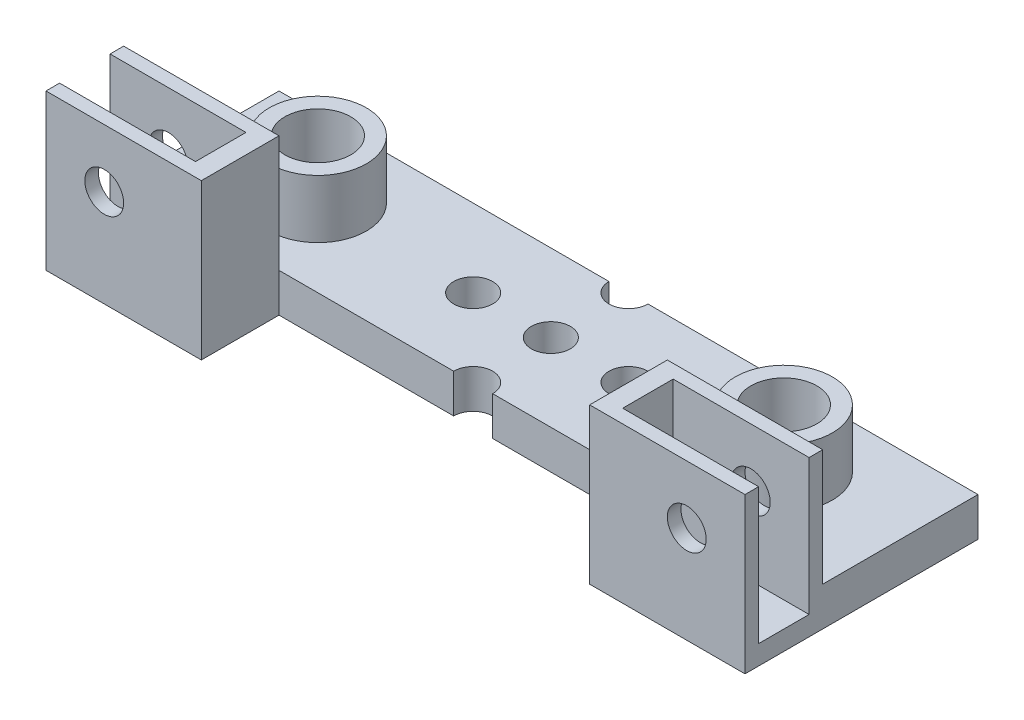
SolidWorks part; units mm, degrees
ref_plane "Front Plane" through (0, 0, 0) normal (0, 0, 1) x (1, 0, 0)
ref_plane "Top Plane" through (0, 0, 0) normal (0, 1, 0) x (1, 0, 0)
ref_plane "Right Plane" through (0, 0, 0) normal (1, 0, 0) x (0, 0, -1)
sketch "Sketch1" plane through (0, 0, 0) normal (0, 1, 0) x (1, 0, 0)
  line L0 (-25, 0) -> (25, 0) construction
  line L1 (25, -20) -> (45, -20)
  line L2 (-25, 20) -> (25, 20) construction
  line L3 (-25, 20) -> (-25, -20)
  line L4 (-25, -20) -> (25, -20) construction
  line L8 (25, -20) -> (25, 20)
  line L9 (0, 10) -> (0, 0) construction
  line L10 (-19.75, -3.35) -> (-25, -3.35) construction
  line L11 (-19.75, -3.35) -> (-19.75, 3.35) construction
  line L12 (-19.75, 3.35) -> (-25, 3.35) construction
  line L13 (-25, -3.35) -> (-25, 3.35) construction
  line L14 (-19.75, -3.35) -> (-25, 3.35) construction
  line L15 (-19.75, 3.35) -> (-25, -3.35) construction
  line L16 (0, 0) -> (0, -10) construction
  line L17 (-22.25, 3.35) -> (-22.25, -3.35) construction
  line L18 (25, -3.35) -> (25, 3.35) construction
  line L19 (19.75, 3.35) -> (25, -3.35) construction
  line L20 (19.75, -3.35) -> (25, 3.35) construction
  line L21 (19.75, -3.35) -> (25, -3.35) construction
  line L22 (22.25, 3.35) -> (22.25, -3.35) construction
  line L23 (19.75, -3.35) -> (19.75, 3.35) construction
  line L24 (19.75, 3.35) -> (25, 3.35) construction
  line L26 (-25, 20) -> (-45, 20)
  line L28 (-25, -20) -> (-45, -20)
  line L29 (-45, 20) -> (-45, -20)
  line L30 (25, 20) -> (45, 20)
  line L31 (45, 20) -> (45, -20)
  line L33 (4.95, 5.2242) -> (-45, 5.2242) construction
  line L34 (-45, 5.2242) -> (-45, 20) construction
  line L35 (45, 5.2242) -> (45, 20) construction
  line L36 (-4.95, 5.2242) -> (45, 5.2242) construction
  line L44 (-45, 10) -> (45, 10)
  line L45 (-45, -10) -> (45, -10)
  circle A4 centre (0, 0) radius 2.51
  circle A5 centre (10, 0) radius 2.51
  circle A6 centre (-10, 0) radius 2.51
  circle A7 centre (0, 10) radius 2.51
  circle A8 centre (0, -10) radius 2.51
  point P16 (-22.375, 0)
  dimension "D2" = 10
  dimension "D4" = 10
  dimension "D7" = 5.02
  dimension "D13" = 50
  dimension "D3" = 20
  dimension "D5" = 5.25
  dimension "D6" = 6.7
  dimension "D8" = 20
  dimension "D9" = 20
  dimension "D10" = 20
  dimension "D11" = 10
  dimension "D12" = 2.5
  dimension "D14" = 20
extrude "Boss-Extrude1" add sketch "Sketch1" along normal blind 5 contours L2 L3 L4 A8 A7 A6 A5 A4 | L33 L34 | L8 L45 L31 L44 | L29 L45 L3 L44 region at (13.755, 0, 9.4615) region at (35, 0, 0) region at (-35, 0, 0)
sketch "Sketch2" plane through (0, 5, 0) normal (0, 1, 0) x (1, 0, 0)
  line L2 (0, 8.46) -> (0, 10) construction
  line L3 (0, -10) -> (0, -23.44) construction
  circle A0 centre (-30, 0) radius 4.25
  circle A1 centre (30, 0) radius 4.25
  circle A2 centre (-30, 0) radius 6.25
  circle A3 centre (30, 0) radius 6.25
  dimension "D2" = 8.5
  dimension "D3" = 8.5
  dimension "D4" = 2
  dimension "D5" = 2
  dimension "D6" = 30
  dimension "D7" = 30
extrude "Boss-Extrude2" add sketch "Sketch2" along normal blind 7.5 contours A2 A0 | A3 A1 | A3 | A2 region at (-36.0732, 5, 0) region at (23.9268, 5, 0)
extrude "Cut-Extrude1" cut sketch "Sketch2<3>" against normal through all contours A0 | A1 region at (-30, 5, 0) region at (30, 5, 0)
sketch "Sketch2<3>" plane through (0, 5, 0) normal (0, 1, 0) x (1, 0, 0) same geometry as "Sketch2"
extrude "Boss-Extrude3" add sketch "Sketch1<3>" along normal blind 20 contours L45 L8 L1 L31 | L45 L29 L28 L3 region at (35, 0, 15) region at (-35, 0, 15)
sketch "Sketch1<3>" plane through (0, 0, 0) normal (0, 1, 0) x (1, 0, 0) same geometry as "Sketch1"
sketch "Sketch3" plane through (0, 20, 0) normal (0, 1, 0) x (1, 0, 0)
  line L0 (-25, -10) -> (-45, -10) construction
  line L1 (-45, -10) -> (-45, -20) construction
  line L2 (-45, -20) -> (-25, -20) construction
  line L3 (-25, -20) -> (-25, -10) construction
  line L4 (45, -10) -> (25, -10) construction
  line L5 (25, -10) -> (25, -20) construction
  line L6 (25, -20) -> (45, -20) construction
  line L7 (45, -20) -> (45, -10) construction
  line L8 (-25, -10) -> (-45, -10)
  line L9 (-45, -10) -> (-45, -20)
  line L10 (-45, -20) -> (-25, -20)
  line L11 (-25, -20) -> (-25, -10)
  line L12 (45, -10) -> (25, -10)
  line L13 (25, -10) -> (25, -20)
  line L14 (25, -20) -> (45, -20)
  line L15 (45, -20) -> (45, -10)
  line L16 (45, -18.25) -> (27.5, -18.25)
  line L17 (27.5, -18.25) -> (27.5, -11.75)
  line L18 (27.5, -11.75) -> (45, -11.75)
  line L19 (0, 0) -> (0, 25) construction
  line L20 (-27.5, -11.75) -> (-45, -11.75)
  line L21 (-27.5, -18.25) -> (-27.5, -11.75)
  line L22 (-45, -18.25) -> (-27.5, -18.25)
  dimension "D1" = 6.5
  dimension "D2" = 1.75
  dimension "D3" = 2.5
extrude "Cut-Extrude2" cut sketch "Sketch3" against normal offset from surface (17.5 mm away) 2.5 contours L18 L17 L16 L15 | L9 L22 L21 L20 region at (-36.25, 20, 15) region at (36.25, 20, 15) up to face at (30, 0, 4.25)
sketch "Sketch4" plane through (0, 0, 20) normal (0, 0, 1) x (1, 0, 0)
  line L0 (32.5, 2.5) -> (35, 20) construction
  line L1 (27.5, 11.25) -> (45, 11.25) construction
  line L2 (36.25, 11.25) -> (36.25, 2.5) construction
  line L3 (0, 0) -> (0, 14.499) construction
  line L4 (25, 0) -> (45, 0)
  line L5 (45, 0) -> (45, 20)
  line L6 (45, 20) -> (25, 20)
  line L7 (25, 20) -> (25, 0)
  line L8 (25, 0) -> (45, 0)
  line L9 (45, 0) -> (45, 20)
  line L10 (45, 20) -> (25, 20)
  line L11 (25, 20) -> (25, 0)
  line L12 (45, 2.5) -> (45, 20)
  line L13 (45, 20) -> (27.5, 20)
  line L14 (27.5, 20) -> (27.5, 2.5)
  line L15 (27.5, 2.5) -> (45, 2.5)
  line L16 (45, 2.5) -> (45, 20)
  line L17 (45, 20) -> (27.5, 20)
  line L18 (27.5, 20) -> (27.5, 2.5)
  line L19 (27.5, 2.5) -> (45, 2.5)
  line L20 (-27.5, 20) -> (-27.5, 2.5)
  line L21 (-27.5, 2.5) -> (-45, 2.5)
  circle A0 centre (37.5, 12.5) radius 2.5
  circle A1 centre (-37.5, 12.5) radius 2.5
  dimension "D3" = 5
  dimension "D4" = 10
  dimension "D5" = 10
  dimension "D1" = 0
  dimension "D2" = 0
extrude "Cut-Extrude3" cut sketch "Sketch4" against normal up to surface (10 mm away) contours A0 | A1 region at (37.5, 12.5, 20) region at (-37.5, 12.5, 20) up to face at (35, 12.5, 10)
